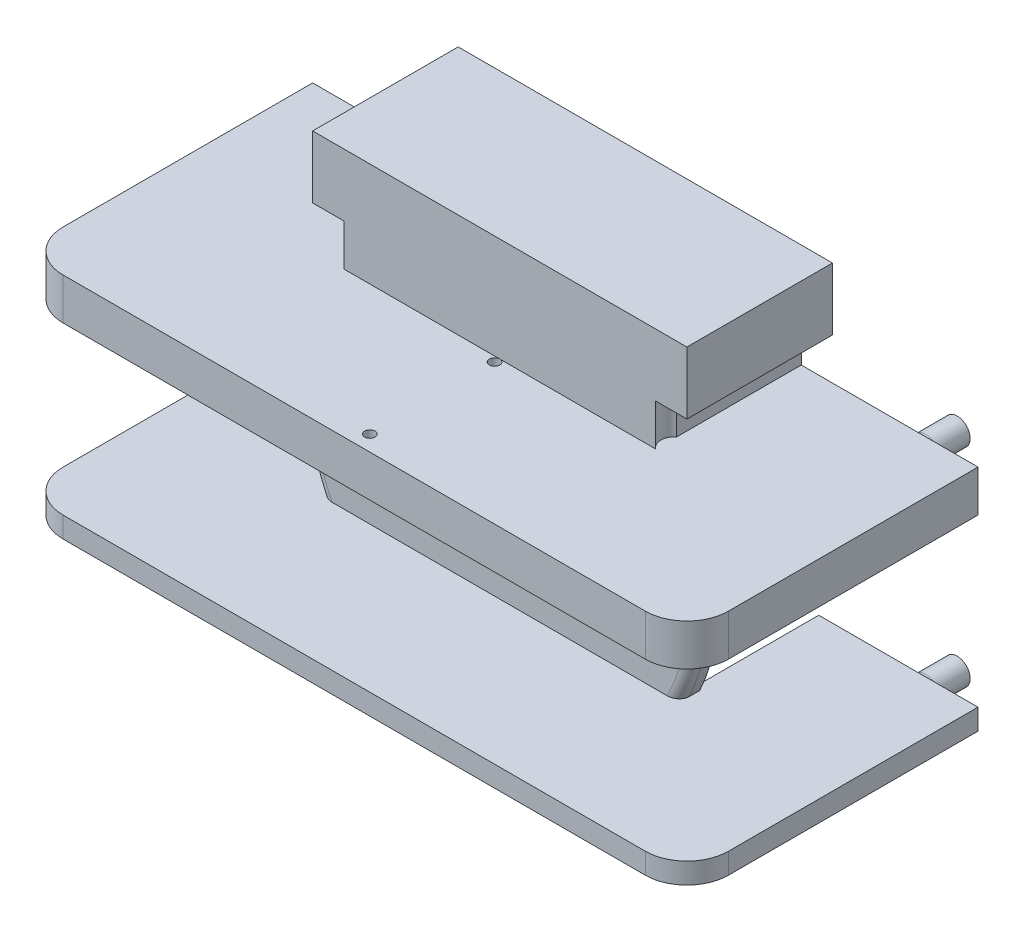
SolidWorks part; units mm, degrees
material "UNOBTANIUM"
ref_plane "Top Plane" through (0, 0, 0) normal (0, 0, 1) x (1, 0, 0)
ref_plane "Right Plane" through (0, 0, 0) normal (0, 1, 0) x (1, 0, 0)
ref_plane "Front Plane" through (0, 0, 0) normal (1, 0, 0) x (0, 0, -1)
ref_axis "x-axis" through (-17.6, 0, 0) along (1, 0, 0)
ref_axis "y-axis" through (0, -9.7375, 0) along (0, 1, 0)
ref_axis "z-axis" through (0, 0, 8.775) along (0, 0, -1)
sketch "Sketch1" plane through (0, 0, 0) normal (0, 0, 1) x (1, 0, 0)
  line L0 (-11, 6) -> (-11, 11)
  line L1 (-11, -6) -> (11, -6)
  line L2 (-11, -6) -> (-11, 6)
  line L3 (-11, 6) -> (11, 6) construction
  line L4 (11, -6) -> (11, 6)
  line L5 (-11, -6) -> (11, 6) construction
  line L6 (-11, 6) -> (11, -6) construction
  line L7 (-11, 11) -> (11, 11)
  line L8 (11, 11) -> (11, 6)
  circle A0 centre (0, 0) radius 8.75 construction
  point P0 (0, 0)
  dimension "D1" = 17.5
  dimension "D2" = 22
  dimension "D3" = 12
  dimension "D4" = 5
extrude "Boss-Extrude1" add sketch "Sketch1" along normal blind 1
sketch "Sketch2" plane through (0, 0, 0) normal (0, 0, -1) x (-1, 0, 0)
  circle A0 centre (0, 0) radius 1.51
  dimension "D1" = 3.02
extrude "Boss-Extrude2" add sketch "Sketch2" along normal blind 5.5
sketch "Sketch3" plane through (0, 0, 0) normal (0, 0, -1) x (-1, 0, 0)
  line L0 (11, -6) -> (-11, 6) construction
  circle A0 centre (0, 0) radius 3.5
  dimension "D1" = 7
extrude "Boss-Extrude3" add sketch "Sketch3" along normal blind 1
sketch "Sketch4" plane through (0, 0, 0) normal (0, 0, -1) x (-1, 0, 0)
  line L0 (11, -6) -> (-11, -6) construction
  line L1 (11, 11) -> (9, 11)
  line L2 (11, 11) -> (11, -6)
  line L3 (11, -6) -> (9, -6)
  line L4 (9, 11) -> (9, -6)
  line L5 (0, -6) -> (0, 11) construction
  line L7 (-9, 11) -> (-9, -6)
  line L8 (-11, -6) -> (-9, -6)
  line L9 (-11, 11) -> (-11, -6)
  line L10 (-11, 11) -> (-9, 11)
  line L11 (11, 11) -> (-11, 11) construction
  dimension "D1" = 2
extrude "Boss-Extrude4" add sketch "Sketch4" along normal blind 6
sketch "Sketch5" plane through (0, 0, 0) normal (0, 0, -1) x (-1, 0, 0)
  line L0 (-9, -6) -> (-9, 11) construction
  line L1 (9, 11) -> (-9, 11)
  line L2 (9, 11) -> (9, 9)
  line L3 (9, 9) -> (-9, 9)
  line L4 (-9, 11) -> (-9, 9)
  dimension "D1" = 2
extrude "Boss-Extrude5" add sketch "Sketch5" along normal up to surface (6 mm away) up to face at (-10, 2.5, -6)
sketch "Sketch6" plane through (11, 0, 0) normal (1, 0, 0) x (0, 0, -1)
  line L0 (-1, -6) -> (-1, 11) construction
  line L1 (6, -6) -> (-1, -6)
  line L2 (6, -6) -> (6, -4)
  line L3 (6, -4) -> (-1, -4)
  line L4 (-1, -6) -> (-1, -4)
  line L6 (6, 11) -> (6, -6) construction
  line L7 (-1, 6) -> (6, 6)
  line L8 (-1, 6) -> (-1, 4)
  line L9 (-1, 4) -> (6, 4)
  line L10 (6, 6) -> (6, 4)
  line L11 (2.5, 4) -> (2.5, -4) construction
  line L12 (0, 0) -> (2.5, 0) construction
  line L13 (0, -6) -> (0, 6) construction
  point P21 (2.5, 0)
  dimension "D1" = 2
extrude "Boss-Extrude6" add sketch "Sketch6" along normal blind 5
mirror "Mirror1" about plane through (0, 0, 0) normal (1, 0, 0) of "Boss-Extrude6"
sketch "Sketch7" plane through (0, 0, -6) normal (0, 0, -1) x (-1, 0, 0)
  line L0 (-9, -6) -> (-9, 9) construction
  line L1 (-9, 0) -> (-9, 9)
  line L2 (-9, 9) -> (0, 9)
  line L3 (-9, 0) -> (-9, -6)
  line L4 (-9, -6) -> (-6.7082, -6)
  line L5 (11, -6) -> (-11, -6) construction
  arc A0 (0, 9) -> (-6.7082, -6) centre (0, 0) ccw
  line M18 (-9, -6) -> (-9, 9)
  line M19 (-9, 9) -> (9, 9)
extrude "Boss-Extrude7" add sketch "Sketch7" against normal up to surface (6 mm away) contours A0 L4 M18 | A0 M19 M18 region at (8.3306, -4.5409, -6) region at (6.9897, 6.9897, -6) up to face at (3.5, 0, 0)
sketch "Sketch8" plane through (0, 0, -6) normal (0, 0, -1) x (-1, 0, 0)
  line L0 (-11, 4) -> (-8.6168, 4)
  line L1 (-11, 4) -> (-11, -4)
  line L2 (-11, -4) -> (-8.6168, -4)
  arc A1 (-8.6168, 4) -> (-8.6168, -4) centre (0, 0) ccw
  dimension "D1" = 9.5
extrude "Cut-Extrude1" cut sketch "Sketch8" against normal through all
sketch "Sketch9" plane through (0, 0, -6) normal (0, 0, -1) x (-1, 0, 0)
  line L0 (-16, -4) -> (-8.6168, -4) construction
  line L1 (-8.0623, 4) -> (-11, 4)
  line L2 (-8.0623, 4) -> (-8.0623, -4)
  line L3 (-8.0623, -4) -> (-11, -4)
  line L4 (-11, 4) -> (-11, -4)
  line L5 (-11, -6) -> (-11, 6) construction
  arc A0 (0, 9) -> (-6.7082, -6) centre (0, 0) ccw construction
  arc A1 (0, 9) -> (-6.7082, -6) centre (0, 0) ccw construction
extrude "Cut-Extrude2" cut sketch "Sketch9" against normal up to surface (6 mm away) up to face at (3.5, 0, 0)
mirror "Mirror2" about plane through (0, 0, 0) normal (1, 0, 0) of "Cut-Extrude2", "Cut-Extrude1", "Boss-Extrude7"
sketch "Sketch21" plane through (0, 0, -6) normal (0, 0, -1) x (-1, 0, 0)
  circle A0 centre (0, 0) radius 9.25
  circle A1 centre (0, 0) radius 9 construction
  circle A2 centre (0, 0) radius 3.5 construction
  circle A3 centre (0, 0) radius 3.5
  dimension "D1" = 0.25
extrude "Cut-Extrude11" cut sketch "Sketch21" against normal up to surface (6 mm away) up to face at (0, -0.7091, 0)
sketch "Sketch10" plane through (0, 0, 1) normal (0, 0, 1) x (1, 0, 0)
  line L0 (-16, -4) -> (-16, -6) construction
  line L1 (16, -6) -> (-16, -6)
  line L2 (16, -6) -> (16, -4)
  line L3 (16, -4) -> (-16, -4)
  line L4 (-16, -6) -> (-16, -4)
  line L5 (-16, -4) -> (-8.6168, -4) construction
  line L7 (-16, 6) -> (16, 6)
  line L8 (-16, 6) -> (-16, 4)
  line L9 (-16, 4) -> (16, 4)
  line L10 (16, 6) -> (16, 4)
extrude "Boss-Extrude8" add sketch "Sketch10" along normal blind 7
fillet "Fillet1" radius 0.5 2 edges at (9.5, 0, 1) (-9.5, 0, 1)
sketch "Sketch11" plane through (0, 0, -6) normal (0, 0, -1) x (-1, 0, 0)
  line L0 (-16, -5) -> (-13, -5) construction
  line L1 (-16, -6) -> (-16, -4) construction
  circle A0 centre (-13, -5) radius 0.625
  dimension "D1" = 1.25
  dimension "D2" = 3
extrude "Boss-Extrude9" add sketch "Sketch11" along normal blind 2
sketch "Sketch14" plane through (0, 0, -6) normal (0, 0, -1) x (-1, 0, 0)
  line L1 (11, 6) -> (7.5, 6)
  line L2 (11, 6) -> (11, 8)
  line L3 (11, 8) -> (7.5, 8)
  line L4 (7.5, 6) -> (7.5, 8)
  line L5 (-11, 6) -> (-7.5, 6)
  line L6 (-11, 6) -> (-11, 8)
  line L7 (-11, 8) -> (-7.5, 8)
  line L8 (-7.5, 6) -> (-7.5, 8)
  dimension "D1" = 15
  dimension "D2" = 2
extrude "Cut-Extrude5" cut sketch "Sketch14" against normal through all
sketch "Sketch12" plane through (0, 0, -6) normal (0, 0, -1) x (-1, 0, 0)
  line L0 (-16, -5) -> (-13, -5) construction
  line L1 (-16, -6) -> (-16, -4) construction
  line L3 (16, -5) -> (13, -5) construction
  line L4 (16, -6) -> (16, -4) construction
  circle A0 centre (13, -5) radius 0.675
  circle A1 centre (-13, -5) radius 0.625 construction
  circle A2 centre (-13, -5) radius 0.625 construction
  dimension "D1" = 1.35
  dimension "D2" = 1.25
extrude "Cut-Extrude3" cut sketch "Sketch12" against normal blind 2.5
sketch "Sketch16" plane through (0, 6, 0) normal (0, 1, 0) x (1, 0, 0)
  line L0 (-7.5, -1) -> (-7.5, 6) construction
  line L1 (-7.5, 0) -> (-7.5, -1)
  arc A1 (-7.5, 0) -> (-7.5, -1) centre (-7.875, -0.5) cw
  dimension "D1" = 0.25
  dimension "D2" = 1
extrude "Cut-Extrude6" cut sketch "Sketch16" along normal blind 2
mirror "Mirror3" about plane through (0, 0, 0) normal (0, 1, 0) of "Boss-Extrude9", "Cut-Extrude3"
mirror "Mirror4" about plane through (0, 0, 0) normal (1, 0, 0) of "Cut-Extrude6"
fillet "Fillet2" radius 0.5 2 edges at (12.375, 5, -6) (13.625, -5, -6)
fillet "Fillet3" radius 0.5 2 edges at (-13.675, 5, -6) (-13.675, -5, -6)
fillet "Fillet4" radius 2 4 edges at (16, -5, 8) (16, 5, 8) (-16, -5, 8) (-16, 5, 8)
sketch "Sketch17" plane through (0, -6, 0) normal (0, -1, 0) x (1, 0, 0)
  line L0 (-16, 6) -> (-16, -6) construction
  line L1 (-14, 8) -> (14, 8) construction
  line L2 (16, 6) -> (16, -6) construction
  line L3 (-16, 6) -> (-16, -6)
  line L4 (-14, 8) -> (14, 8)
  line L5 (16, 6) -> (16, -6)
  line L6 (14.5, 6) -> (14.5, -6)
  line L8 (-14, 6.5) -> (14, 6.5)
  line L9 (-14.5, 6) -> (-14.5, -6)
  line L10 (14.5, -6) -> (16, -6)
  line L11 (-14.5, -6) -> (-16, -6)
  arc A0 (-14, 8) -> (-16, 6) centre (-14, 6) ccw construction
  arc A1 (16, 6) -> (14, 8) centre (14, 6) ccw construction
  arc A2 (-14, 8) -> (-16, 6) centre (-14, 6) ccw
  arc A3 (16, 6) -> (14, 8) centre (14, 6) ccw
  arc A4 (14.5, 6) -> (14, 6.5) centre (14, 6) ccw
  arc A5 (-14, 6.5) -> (-14.5, 6) centre (-14, 6) ccw
  dimension "D1" = 1.5
extrude "Cut-Extrude7" cut sketch "Sketch17" against normal blind 1 and the other way through all
sketch "Sketch19" plane through (0, 6, 0) normal (0, 1, 0) x (1, 0, 0)
  line L0 (7.5, -1) -> (-7.5, -1) construction
  line L1 (0, -1.25) -> (0, -1) construction
  line L2 (7.5, -1) -> (-7.5, -1) construction
  circle A0 centre (0, -1.25) radius 0.25
  circle A1 centre (0, -7.25) radius 0.25
  point P4 (0, -1)
  dimension "D1" = 0.5
  dimension "D2" = 6
extrude "Cut-Extrude9" cut sketch "Sketch19" against normal up to surface (2 mm away) up to face at (0.0155, 4, -0.8002)
sketch "Sketch20" plane through (0, 0, -6) normal (0, 0, -1) x (-1, 0, 0)
  line L0 (-7.5, 8) -> (-11, 8) construction
  line L1 (-11, 11) -> (-9, 11)
  line L2 (-11, 11) -> (-11, 8)
  line L3 (-11, 8) -> (-9, 8)
  line L4 (-9, 11) -> (-9, 8)
  line L5 (11, 11) -> (-11, 11) construction
  line L6 (11, 8) -> (9, 8)
  line L7 (11, 8) -> (11, 11)
  line L8 (11, 11) -> (9, 11)
  line L9 (9, 8) -> (9, 11)
  dimension "D1" = 2
extrude "Cut-Extrude10" cut sketch "Sketch20" against normal through all
equation "\"D1@Sketch12\"=\"D2@Sketch12\"+.1"
